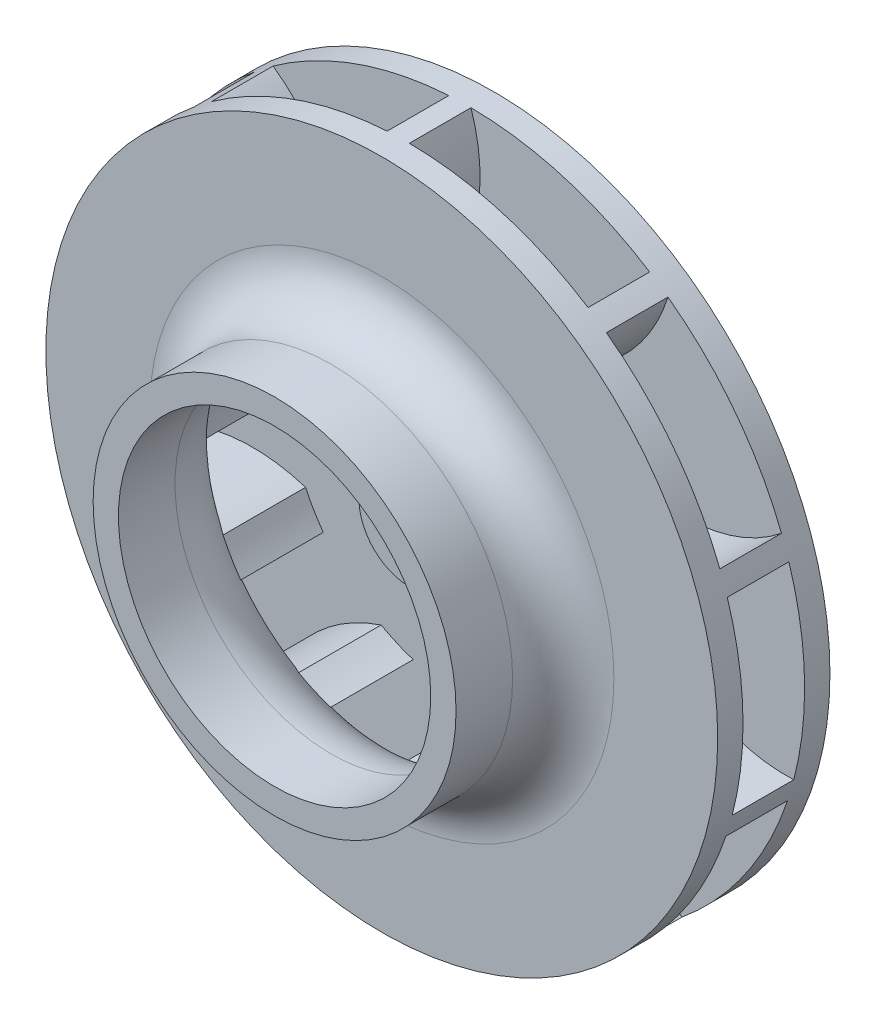
SolidWorks part; units mm, degrees
ref_plane "Front Plane" through (0, 0, 0) normal (0, 0, 1) x (1, 0, 0)
ref_plane "Top Plane" through (0, 0, 0) normal (0, 1, 0) x (1, 0, 0)
ref_plane "Right Plane" through (0, 0, 0) normal (1, 0, 0) x (0, 0, -1)
sketch "Sketch1" plane through (0, 0, 0) normal (0, 0, 1) x (1, 0, 0)
  circle A0 centre (0, 0) radius 39.8
  dimension "D1" = 79.6
extrude "Body" add sketch "Sketch1" along normal blind 3
sketch "Sketch2" plane through (0, 0, 3) normal (0, 0, 1) x (1, 0, 0)
  circle A0 centre (0, 0) radius 6
  dimension "D1" = 12
extrude "Spigot" add sketch "Sketch2" along normal blind 7
fillet "Fillet" radius 7 1 edges at (6, 0, 3)
hole_wizard "M6 Tapped Hole" positions "Sketch3" profile "Sketch4" tap size "M6" standard "ISO" end condition through all
sketch "Sketch3" plane through (0, 0, 10) normal (0, 0, 1) x (1, 0, 0)
  point P0 (0, 0)
sketch "Sketch4" plane through (0, 0, 10) normal (1, 0, 0) x (0, -1, 0)
  line L0 (0, 0) -> (0, 10)
  line L1 (0, 10) -> (2.5, 10)
  line L2 (2.5, 10) -> (2.5, 0.525)
  line L3 (2.5, 0.525) -> (3.025, 0)
  line L5 (3.025, 0) -> (0, 0)
  line L6 (-2.5, 0.525) -> (-3.025, 0) construction
  line L11 (0, -6.35) -> (0, 107.95) construction
  dimension "Thru Tap Drill Dia." = 5
  dimension "Thru Tap Drill Depth" = 10
  dimension "Near C'Sink Dia." = 6.05
  dimension "Near C'Sink Angle" = 90
cosmetic thread "Hole Thread1" parameters "D2"=6
sketch "Sketch5" plane through (0, 0, 3) normal (0, 0, 1) x (1, 0, 0)
  line L0 (0, 0) -> (-50.0598, 0) construction
  line L1 (-21.3, 0) -> (-39.6501, -9.161) construction
  line L2 (0, 0) -> (-49.0205, 28.559) construction
  line L3 (-21.3, 0) -> (-49.0205, 28.559) construction
  line L4 (-24.5102, 14.2795) -> (-62.9991, -51.7853) construction
  arc A1 (-20.8977, 4.1203) -> (-21.3, 0) centre (0, 0) ccw
  arc A2 (-21.3, 0) -> (-38.5155, 10.0297) centre (-37.558, -8.1166) ccw
  arc A4 (-37.7683, 12.5538) -> (-38.5155, 10.0297) centre (0, 0) ccw
  arc A6 (-20.8977, 4.1203) -> (-37.7683, 12.5538) centre (-37.558, -8.1166) ccw
  dimension "D2" = 42.6
  dimension "D3" = 26.53
  dimension "D4" = 39.8
  dimension "D5" = 134.146
extrude "Blade" add sketch "Sketch5" along normal blind 10
pattern_circular "CirPattern1" count 10 over 360 about axis through (0, 0, 10) along (0, 0, 1) of "Blade"
sketch "Sketch6" plane through (0, 0, 0) normal (1, 0, 0) x (0, 0, -1)
  line L1 (-13.3, 39.8) -> (-13.3, 27.5)
  line L3 (0, -39.8) -> (0, 39.8) construction
  line L4 (-19.3, 21.5) -> (-26, 21.5)
  line L5 (-26, 21.5) -> (-26, 18.5)
  line L6 (-26, 18.5) -> (-19.3, 18.5)
  line L7 (-10.3, 39.8) -> (-10.3, 27.5)
  line L8 (-58.0738, 0) -> (14.6352, 0) construction
  line L10 (-13.3, 39.8) -> (-10.3, 39.8)
  line L12 (0, 39.8) -> (-21.647, 39.8) construction
  arc A0 (-19.3, 21.5) -> (-13.3, 27.5) centre (-19.3, 27.5) ccw
  arc A1 (-19.3, 18.5) -> (-10.3, 27.5) centre (-19.3, 27.5) ccw
  point P2 (-26, 20)
  dimension "D6" = 6
  dimension "D7" = 9
  dimension "D8" = 21.5
  dimension "D2" = 3
  dimension "D3" = 13.3
  dimension "D4" = 26
  dimension "D5" = 3
revolve "Revolve1" add sketch "Sketch6" angle 360 about L8
